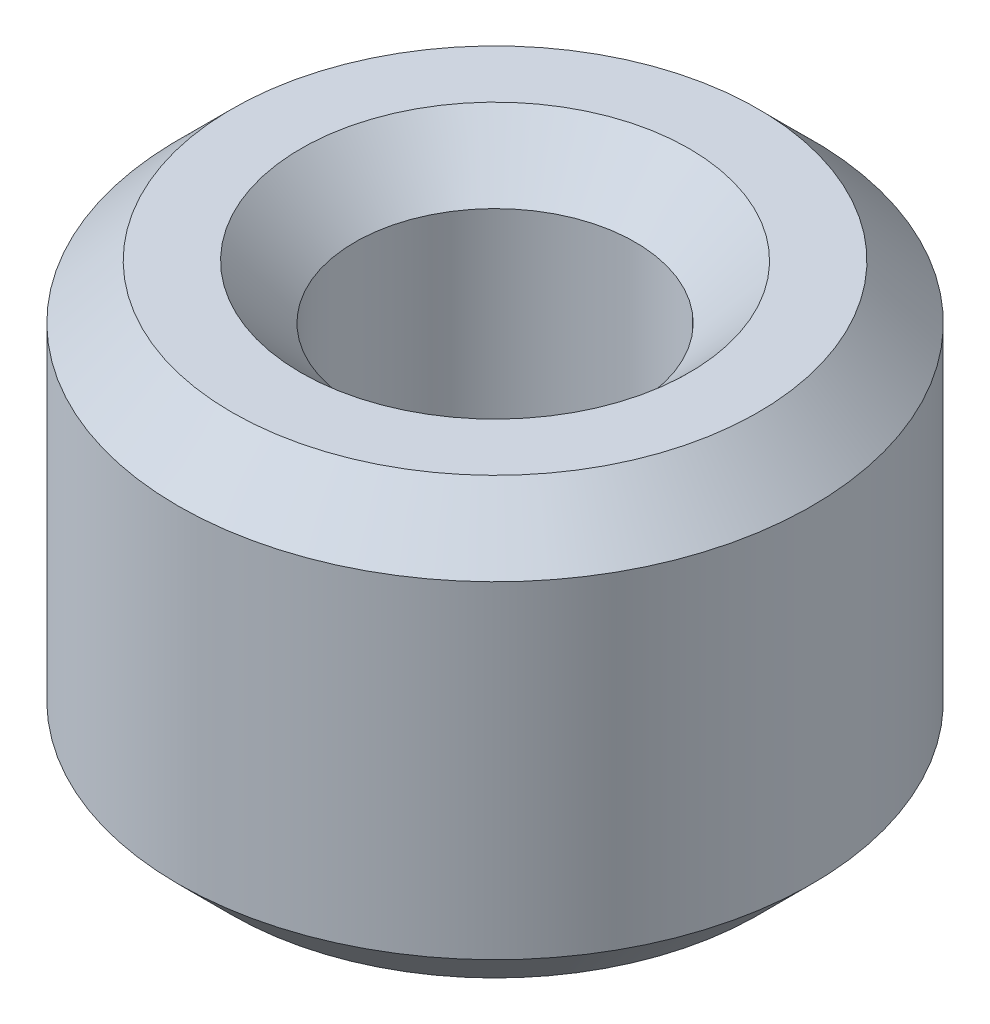
SolidWorks part; units mm, degrees
ref_plane "Front Plane" through (0, 0, 0) normal (0, 0, 1) x (1, 0, 0)
ref_plane "Top Plane" through (0, 0, 0) normal (0, 1, 0) x (1, 0, 0)
ref_plane "Right Plane" through (0, 0, 0) normal (1, 0, 0) x (0, 0, -1)
sketch "Sketch1" plane through (0, 0, 0) normal (0, 1, 0) x (1, 0, 0)
  circle A0 centre (0, 0) radius 15
  dimension "SLEEVE_OD" = 30
extrude "Boss-Extrude1" add sketch "Sketch1" along normal blind 20.6002
sketch "Sketch2" plane through (0, 0, 0) normal (0, 1, 0) x (1, 0, 0)
  circle A0 centre (0, 0) radius 6.6313
  dimension "BORE_D" = 13.2626
extrude "Cut-Extrude1" cut sketch "Sketch2" along normal through all
chamfer "Chamfer1" distance 2.5553 angle 45 4 edges at (0, 20.6002, 6.6313) (0, 0, 6.6313) (0, 0, 15) (0, 20.6002, 15)
